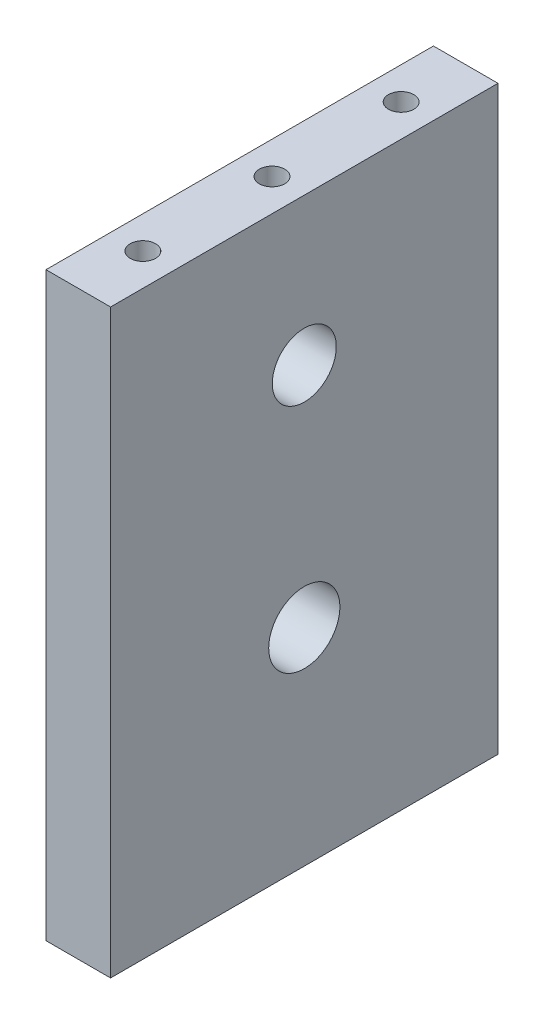
SolidWorks part; units mm, degrees
ref_plane "Front Plane" through (0, 0, 0) normal (0, 0, 1) x (1, 0, 0)
ref_plane "Top Plane" through (0, 0, 0) normal (0, 1, 0) x (1, 0, 0)
ref_plane "Right Plane" through (0, 0, 0) normal (1, 0, 0) x (0, 0, -1)
sketch "Sketch1" plane through (0, 0, 0) normal (0, 0, 1) x (1, 0, 0)
  line L0 (0, 0) -> (0, 76.2)
  line L5 (0, 76.2) -> (88.098, 76.2)
  line L6 (88.098, 76.2) -> (88.098, 101.6)
  line L7 (0, 0) -> (6.35, 0)
  line L8 (6.35, 0) -> (6.35, 76.2)
  line L9 (6.35, 76.2) -> (6.35, 69.85)
  line L10 (6.35, 69.85) -> (101.1141, 69.85)
  line L11 (88.098, 101.6) -> (94.448, 101.6)
  line L12 (94.448, 101.6) -> (94.448, 69.85)
  dimension "D1" = 25.4
  dimension "D2" = 76.2
extrude "Boss-Extrude1" add sketch "Sketch1" along normal blind 38.1 contours L7 L8 L5 L0 | L12 L11 L6 L5 L8 L10 region at (3.175, 38.1, 0) region at (47.224, 75.2636, 0)
sketch "Sketch2" plane through (0, 0, 0) normal (-1, 0, 0) x (0, 0, 1)
  line L0 (19.05, 20.32) -> (19.05, 42.672)
  line L1 (0, 0) -> (0, 76.2) construction
  line L2 (38.1, 0) -> (0, 0)
  line L3 (38.1, 0) -> (38.1, 50.8)
  line L4 (38.1, 50.8) -> (0, 50.8)
  line L5 (0, 0) -> (0, 50.8)
  line L6 (38.1, 0) -> (38.1, 20.32)
  line L7 (38.1, 20.32) -> (0, 20.32)
  circle A0 centre (19.05, 20.32) radius 3.5
  circle A1 centre (19.05, 42.672) radius 3.148
  dimension "D1" = 22.352
  dimension "D2" = 20.32
  dimension "D3" = 7
  dimension "D4" = 6.296
extrude "Cut-Extrude1" cut sketch "Sketch2" against normal blind 6.35 contours A0
extrude "Cut-Extrude2" cut sketch "Sketch2<4>" against normal blind 6.35 contours A1
sketch "Sketch2<4>" plane through (0, 0, 0) normal (-1, 0, 0) x (0, 0, 1) same geometry as "Sketch2"
sketch "Sketch4" plane through (0, 0, 38.1) normal (0, 0, 1) x (1, 0, 0)
  line L0 (0, 0) -> (0, 76.2) construction
  line L13 (94.448, 101.6) -> (0, 101.6)
  line L14 (94.448, 101.6) -> (94.448, 69.85)
  line L15 (94.448, 69.85) -> (0, 69.85)
  line L16 (0, 101.6) -> (0, 69.85)
extrude "Cut-Extrude5" cut sketch "Sketch4" against normal blind 76.2
sketch "Sketch5" plane through (6.35, 0, 0) normal (1, 0, 0) x (0, 0, -1)
  line L0 (0, 0) -> (0, 69.85) construction
  line L1 (-38.1, 69.85) -> (0, 69.85)
  line L2 (-38.1, 69.85) -> (-38.1, 57.15)
  line L3 (-38.1, 57.15) -> (0, 57.15)
  line L4 (0, 69.85) -> (0, 57.15)
  point P7 (-50.5914, -55.0109)
  dimension "D1" = 12.7
extrude "Cut-Extrude6" cut sketch "Sketch5" against normal blind 6.35 contours L1 L4 L3 L2
sketch "Sketch8" plane through (0, 57.15, 0) normal (0, 1, 0) x (1, 0, 0)
  line L0 (3.175, 0) -> (3.175, -38.1)
  line L1 (0, 0) -> (6.35, 0) construction
  line L2 (0, -38.1) -> (6.35, -38.1) construction
  line L3 (3.175, -38.1) -> (3.175, -31.75)
  line L4 (3.175, 0) -> (3.175, -6.35)
  circle A0 centre (3.175, -6.35) radius 1.25
  circle A1 centre (3.175, -19.05) radius 1.25
  circle A2 centre (3.175, -31.75) radius 1.25
  dimension "D3" = 2.5
  dimension "D4" = 2.5
  dimension "D5" = 2.5
  dimension "D1" = 6.35
  dimension "D2" = 6.35
extrude "Cut-Extrude7" cut sketch "Sketch8" against normal blind 6.35 contours L0 A2 | L0 A2 | A0 | A1 region at (3.7055, 57.15, 31.75) region at (2.6445, 57.15, 31.75)
